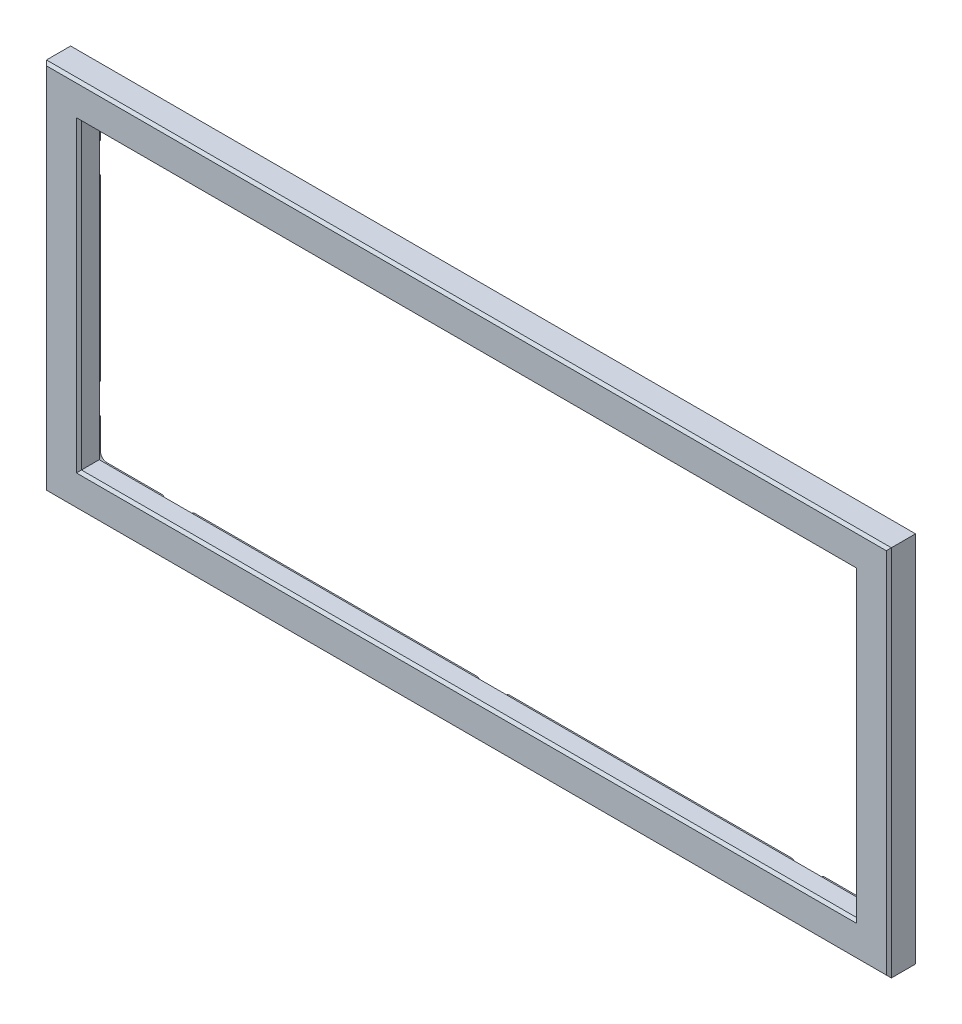
SolidWorks part; units mm, degrees
material "7075-T6 (SN)"
ref_plane "Front Plane" through (0, 0, 0) normal (0, 0, 1) x (1, 0, 0)
ref_plane "Top Plane" through (0, 0, 0) normal (0, 1, 0) x (1, 0, 0)
ref_plane "Right Plane" through (0, 0, 0) normal (1, 0, 0) x (0, 0, -1)
sketch "Sketch1" plane through (0, 0, 0) normal (0, 0, 1) x (1, 0, 0)
  line L43 (-4.2125, 142.325) -> (328.0625, 142.325)
  line L44 (-4.2125, 142.325) -> (-4.2125, -4.2125)
  line L45 (-4.2125, -4.2125) -> (328.0625, -4.2125)
  line L46 (328.0625, 142.325) -> (328.0625, -4.2125)
  line L104 (313.8, 130.5625) -> (292.3, 130.5625)
  line L105 (290.8, 132.0625) -> (290.8, 132.5625)
  line L106 (280.8, 132.5625) -> (280.8, 132.0625)
  line L107 (279.3, 130.5625) -> (168.425, 130.5625)
  line L108 (166.925, 132.0625) -> (166.925, 132.5625)
  line L109 (156.925, 132.5625) -> (156.925, 132.0625)
  line L110 (155.425, 130.5625) -> (44.55, 130.5625)
  line L111 (43.05, 132.0625) -> (43.05, 132.5625)
  line L112 (33.05, 132.5625) -> (33.05, 132.0625)
  line L113 (31.55, 130.5625) -> (10.05, 130.5625)
  line L114 (7.55, 128.0625) -> (7.55, 116.5625)
  line L115 (6.05, 115.0625) -> (5.55, 115.0625)
  line L116 (5.55, 105.0625) -> (6.05, 105.0625)
  line L117 (7.55, 103.5625) -> (7.55, 34.55)
  line L118 (6.05, 33.05) -> (5.55, 33.05)
  line L119 (5.55, 23.05) -> (6.05, 23.05)
  line L120 (7.55, 21.55) -> (7.55, 10.05)
  line L121 (10.05, 7.55) -> (31.55, 7.55)
  line L122 (33.05, 6.05) -> (33.05, 5.55)
  line L123 (43.05, 5.55) -> (43.05, 6.05)
  line L124 (44.55, 7.55) -> (155.425, 7.55)
  line L125 (156.925, 6.05) -> (156.925, 5.55)
  line L126 (166.925, 5.55) -> (166.925, 6.05)
  line L127 (168.425, 7.55) -> (279.3, 7.55)
  line L128 (280.8, 6.05) -> (280.8, 5.55)
  line L129 (290.8, 5.55) -> (290.8, 6.05)
  line L130 (292.3, 7.55) -> (313.8, 7.55)
  line L131 (316.3, 10.05) -> (316.3, 21.55)
  line L132 (317.8, 23.05) -> (318.3, 23.05)
  line L133 (318.3, 33.05) -> (317.8, 33.05)
  line L134 (316.3, 34.55) -> (316.3, 103.5625)
  line L135 (317.8, 105.0625) -> (318.3, 105.0625)
  line L136 (318.3, 115.0625) -> (317.8, 115.0625)
  line L137 (316.3, 116.5625) -> (316.3, 128.0625)
  line L138 (313.8, 130.5625) -> (292.3, 130.5625)
  line L139 (290.8, 132.0625) -> (290.8, 132.5625)
  line L140 (280.8, 132.5625) -> (280.8, 132.0625)
  line L141 (279.3, 130.5625) -> (168.425, 130.5625)
  line L142 (166.925, 132.0625) -> (166.925, 132.5625)
  line L143 (156.925, 132.5625) -> (156.925, 132.0625)
  line L144 (155.425, 130.5625) -> (44.55, 130.5625)
  line L145 (43.05, 132.0625) -> (43.05, 132.5625)
  line L146 (33.05, 132.5625) -> (33.05, 132.0625)
  line L147 (31.55, 130.5625) -> (10.05, 130.5625)
  line L148 (7.55, 128.0625) -> (7.55, 116.5625)
  line L149 (6.05, 115.0625) -> (5.55, 115.0625)
  line L150 (5.55, 105.0625) -> (6.05, 105.0625)
  line L151 (7.55, 103.5625) -> (7.55, 34.55)
  line L152 (6.05, 33.05) -> (5.55, 33.05)
  line L153 (5.55, 23.05) -> (6.05, 23.05)
  line L154 (7.55, 21.55) -> (7.55, 10.05)
  line L155 (10.05, 7.55) -> (31.55, 7.55)
  line L156 (33.05, 6.05) -> (33.05, 5.55)
  line L157 (43.05, 5.55) -> (43.05, 6.05)
  line L158 (44.55, 7.55) -> (155.425, 7.55)
  line L159 (156.925, 6.05) -> (156.925, 5.55)
  line L160 (166.925, 5.55) -> (166.925, 6.05)
  line L161 (168.425, 7.55) -> (279.3, 7.55)
  line L162 (280.8, 6.05) -> (280.8, 5.55)
  line L163 (290.8, 5.55) -> (290.8, 6.05)
  line L164 (292.3, 7.55) -> (313.8, 7.55)
  line L165 (316.3, 10.05) -> (316.3, 21.55)
  line L166 (317.8, 23.05) -> (318.3, 23.05)
  line L167 (318.3, 33.05) -> (317.8, 33.05)
  line L168 (316.3, 34.55) -> (316.3, 103.5625)
  line L169 (317.8, 105.0625) -> (318.3, 105.0625)
  line L170 (318.3, 115.0625) -> (317.8, 115.0625)
  line L171 (316.3, 116.5625) -> (316.3, 128.0625)
  arc A136 (290.8, 132.0625) -> (292.3, 130.5625) centre (292.3, 132.0625) ccw
  arc A137 (290.8, 132.5625) -> (280.8, 132.5625) centre (285.8, 132.5625) ccw
  arc A138 (279.3, 130.5625) -> (280.8, 132.0625) centre (279.3, 132.0625) ccw
  arc A139 (166.925, 132.0625) -> (168.425, 130.5625) centre (168.425, 132.0625) ccw
  arc A140 (166.925, 132.5625) -> (156.925, 132.5625) centre (161.925, 132.5625) ccw
  arc A141 (155.425, 130.5625) -> (156.925, 132.0625) centre (155.425, 132.0625) ccw
  arc A142 (43.05, 132.0625) -> (44.55, 130.5625) centre (44.55, 132.0625) ccw
  arc A143 (43.05, 132.5625) -> (33.05, 132.5625) centre (38.05, 132.5625) ccw
  arc A144 (31.55, 130.5625) -> (33.05, 132.0625) centre (31.55, 132.0625) ccw
  arc A145 (10.05, 130.5625) -> (7.55, 128.0625) centre (10.05, 128.0625) ccw
  arc A146 (6.05, 115.0625) -> (7.55, 116.5625) centre (6.05, 116.5625) ccw
  arc A147 (5.55, 115.0625) -> (5.55, 105.0625) centre (5.55, 110.0625) ccw
  arc A148 (7.55, 103.5625) -> (6.05, 105.0625) centre (6.05, 103.5625) ccw
  arc A149 (6.05, 33.05) -> (7.55, 34.55) centre (6.05, 34.55) ccw
  arc A150 (5.55, 33.05) -> (5.55, 23.05) centre (5.55, 28.05) ccw
  arc A151 (7.55, 21.55) -> (6.05, 23.05) centre (6.05, 21.55) ccw
  arc A152 (7.55, 10.05) -> (10.05, 7.55) centre (10.05, 10.05) ccw
  arc A153 (33.05, 6.05) -> (31.55, 7.55) centre (31.55, 6.05) ccw
  arc A154 (33.05, 5.55) -> (43.05, 5.55) centre (38.05, 5.55) ccw
  arc A155 (44.55, 7.55) -> (43.05, 6.05) centre (44.55, 6.05) ccw
  arc A156 (156.925, 6.05) -> (155.425, 7.55) centre (155.425, 6.05) ccw
  arc A157 (156.925, 5.55) -> (166.925, 5.55) centre (161.925, 5.55) ccw
  arc A158 (168.425, 7.55) -> (166.925, 6.05) centre (168.425, 6.05) ccw
  arc A159 (280.8, 6.05) -> (279.3, 7.55) centre (279.3, 6.05) ccw
  arc A160 (280.8, 5.55) -> (290.8, 5.55) centre (285.8, 5.55) ccw
  arc A161 (292.3, 7.55) -> (290.8, 6.05) centre (292.3, 6.05) ccw
  arc A162 (313.8, 7.55) -> (316.3, 10.05) centre (313.8, 10.05) ccw
  arc A163 (317.8, 23.05) -> (316.3, 21.55) centre (317.8, 21.55) ccw
  arc A164 (318.3, 23.05) -> (318.3, 33.05) centre (318.3, 28.05) ccw
  arc A165 (316.3, 34.55) -> (317.8, 33.05) centre (317.8, 34.55) ccw
  arc A166 (317.8, 105.0625) -> (316.3, 103.5625) centre (317.8, 103.5625) ccw
  arc A167 (318.3, 105.0625) -> (318.3, 115.0625) centre (318.3, 110.0625) ccw
  arc A168 (316.3, 116.5625) -> (317.8, 115.0625) centre (317.8, 116.5625) ccw
  arc A169 (316.3, 128.0625) -> (313.8, 130.5625) centre (313.8, 128.0625) ccw
  arc A170 (290.8, 132.0625) -> (292.3, 130.5625) centre (292.3, 132.0625) ccw
  arc A171 (290.8, 132.5625) -> (280.8, 132.5625) centre (285.8, 132.5625) ccw
  arc A172 (279.3, 130.5625) -> (280.8, 132.0625) centre (279.3, 132.0625) ccw
  arc A173 (166.925, 132.0625) -> (168.425, 130.5625) centre (168.425, 132.0625) ccw
  arc A174 (166.925, 132.5625) -> (156.925, 132.5625) centre (161.925, 132.5625) ccw
  arc A175 (155.425, 130.5625) -> (156.925, 132.0625) centre (155.425, 132.0625) ccw
  arc A176 (43.05, 132.0625) -> (44.55, 130.5625) centre (44.55, 132.0625) ccw
  arc A177 (43.05, 132.5625) -> (33.05, 132.5625) centre (38.05, 132.5625) ccw
  arc A178 (31.55, 130.5625) -> (33.05, 132.0625) centre (31.55, 132.0625) ccw
  arc A179 (10.05, 130.5625) -> (7.55, 128.0625) centre (10.05, 128.0625) ccw
  arc A180 (6.05, 115.0625) -> (7.55, 116.5625) centre (6.05, 116.5625) ccw
  arc A181 (5.55, 115.0625) -> (5.55, 105.0625) centre (5.55, 110.0625) ccw
  arc A182 (7.55, 103.5625) -> (6.05, 105.0625) centre (6.05, 103.5625) ccw
  arc A183 (6.05, 33.05) -> (7.55, 34.55) centre (6.05, 34.55) ccw
  arc A184 (5.55, 33.05) -> (5.55, 23.05) centre (5.55, 28.05) ccw
  arc A185 (7.55, 21.55) -> (6.05, 23.05) centre (6.05, 21.55) ccw
  arc A186 (7.55, 10.05) -> (10.05, 7.55) centre (10.05, 10.05) ccw
  arc A187 (33.05, 6.05) -> (31.55, 7.55) centre (31.55, 6.05) ccw
  arc A188 (33.05, 5.55) -> (43.05, 5.55) centre (38.05, 5.55) ccw
  arc A189 (44.55, 7.55) -> (43.05, 6.05) centre (44.55, 6.05) ccw
  arc A190 (156.925, 6.05) -> (155.425, 7.55) centre (155.425, 6.05) ccw
  arc A191 (156.925, 5.55) -> (166.925, 5.55) centre (161.925, 5.55) ccw
  arc A192 (168.425, 7.55) -> (166.925, 6.05) centre (168.425, 6.05) ccw
  arc A193 (280.8, 6.05) -> (279.3, 7.55) centre (279.3, 6.05) ccw
  arc A194 (280.8, 5.55) -> (290.8, 5.55) centre (285.8, 5.55) ccw
  arc A195 (292.3, 7.55) -> (290.8, 6.05) centre (292.3, 6.05) ccw
  arc A196 (313.8, 7.55) -> (316.3, 10.05) centre (313.8, 10.05) ccw
  arc A197 (317.8, 23.05) -> (316.3, 21.55) centre (317.8, 21.55) ccw
  arc A198 (318.3, 23.05) -> (318.3, 33.05) centre (318.3, 28.05) ccw
  arc A199 (316.3, 34.55) -> (317.8, 33.05) centre (317.8, 34.55) ccw
  arc A200 (317.8, 105.0625) -> (316.3, 103.5625) centre (317.8, 103.5625) ccw
  arc A201 (318.3, 105.0625) -> (318.3, 115.0625) centre (318.3, 110.0625) ccw
  arc A202 (316.3, 116.5625) -> (317.8, 115.0625) centre (317.8, 116.5625) ccw
  arc A203 (316.3, 128.0625) -> (313.8, 130.5625) centre (313.8, 128.0625) ccw
  dimension "D2" = 4.7625
  dimension "D3" = 4.7625
  dimension "D4" = 4.7625
  dimension "D5" = 4.7625
  dimension "D1" = 0.5
extrude "Boss-Extrude1" add sketch "Sketch1" against normal mid plane 2.5
sketch "Sketch2" plane through (0, 0, 1.25) normal (0, 0, 1) x (1, 0, 0)
  line L28 (7.55, 128.0625) -> (7.55, 116.5625) construction
  line L30 (161.925, 142.325) -> (161.925, -4.2125) construction
  line L31 (-4.2125, 69.0562) -> (328.0625, 69.0562) construction
  line L32 (328.0625, -4.2125) -> (328.0625, 142.325) construction
  line L36 (328.0625, 142.325) -> (-4.2125, 142.325)
  line L38 (-4.2125, 142.325) -> (-4.2125, -4.2125)
  line L39 (9.55, 128.5625) -> (314.3, 128.5625)
  line L40 (-4.2125, -4.2125) -> (328.0625, -4.2125)
  line L41 (9.55, 128.5625) -> (9.55, 9.55)
  line L42 (328.0625, -4.2125) -> (328.0625, 142.325)
  line L43 (9.55, 9.55) -> (314.3, 9.55)
  line L44 (328.0625, 142.325) -> (-4.2125, 142.325)
  line L46 (-4.2125, 142.325) -> (-4.2125, -4.2125)
  line L48 (-4.2125, -4.2125) -> (328.0625, -4.2125)
  line L50 (328.0625, -4.2125) -> (328.0625, 142.325)
  line L52 (314.3, 128.5625) -> (314.3, 9.55)
  dimension "D2" = 11.7625
  dimension "D3" = 13.7625
  dimension "D4" = 13.7625
  dimension "D5" = 13.7625
  dimension "D6" = 13.7625
extrude "Boss-Extrude2" add sketch "Sketch2" along normal blind 8 contours L50 L44 L46 L48 region at (324.431, 69.0562, 1.25)
chamfer "Chamfer1" distance 1 angle 45 8 edges at (328.0625, 69.0562, 9.25) (161.925, -4.2125, 9.25) (-4.2125, 69.0562, 9.25) (161.925, 142.325, 9.25) (9.55, 69.0562, 9.25) (161.925, 9.55, 9.25) (314.3, 69.0562, 9.25) (161.925, 128.5625, 9.25)
hole_wizard "M2.5 Tapped Hole1" positions "Sketch3" profile "Sketch4" tap size "M2.5" standard "DIN"
sketch "Sketch3" plane through (0, 0, 1.25) normal (0, 0, -1) x (-1, 0, 0)
  arc A1 (-290.8, 5.55) -> (-280.8, 5.55) centre (-285.8, 5.55) ccw construction
  point P37 (-285.8, 132.5625)
  point P40 (-318.3, 110.0625)
  point P43 (-318.3, 28.05)
  point P46 (-285.8, 5.55)
  point P49 (-161.925, 5.55)
  point P52 (-38.05, 5.55)
  point P55 (-5.55, 28.05)
  point P58 (-38.05, 132.5625)
  point P61 (-5.55, 110.0625)
  point P65 (-161.925, 132.5625)
sketch "Sketch4" plane through (285.8, 132.5625, 1.25) normal (1, 0, 0) x (0, 1, 0)
  line L0 (0, 0) -> (0, 6.9659)
  line L1 (0, 6.9659) -> (1.025, 6.35)
  line L2 (1.025, 6.35) -> (1.025, 0.475)
  line L3 (1.025, 0.475) -> (1.5, 0)
  line L5 (1.5, 0) -> (0, 0)
  line L6 (-1.025, 0.475) -> (-1.5, 0) construction
  line L10 (0, 6.9659) -> (-1.025, 6.35) construction
  line L11 (0, -6.35) -> (0, 107.95) construction
  dimension "Tap Drill Dia." = 2.05
  dimension "Tap Drill Depth" = 6.35
  dimension "Near C'Sink Dia." = 3
  dimension "Near C'Sink Angle" = 90
  dimension "Drill Angle" = 118
cosmetic thread "Hole Thread44" parameters "D1"=5, "D2"=2.5
cosmetic thread "Hole Thread45" parameters "D1"=5, "D2"=2.5
cosmetic thread "Hole Thread46" parameters "D1"=5, "D2"=2.5
cosmetic thread "Hole Thread47" parameters "D1"=5, "D2"=2.5
cosmetic thread "Hole Thread48" parameters "D1"=5, "D2"=2.5
cosmetic thread "Hole Thread49" parameters "D1"=5, "D2"=2.5
cosmetic thread "Hole Thread50" parameters "D1"=5, "D2"=2.5
cosmetic thread "Hole Thread51" parameters "D1"=5, "D2"=2.5
cosmetic thread "Hole Thread52" parameters "D1"=5, "D2"=2.5
cosmetic thread "Hole Thread53" parameters "D1"=5, "D2"=2.5
hole_wizard "M3 Tapped Hole1" positions "Sketch5" profile "Sketch6" tap size "M3" standard "DIN"
sketch "Sketch5" plane through (0, 0, -1.25) normal (0, 0, -1) x (-1, 0, 0)
  point P0 (-268.0625, 138.325)
  point P3 (-324.0625, 138.325)
  point P6 (-324.0625, 88.325)
  point P9 (-324.0625, 49.7874)
  point P12 (-324.0625, -0.2126)
  point P15 (-268.0625, -0.2126)
  point P18 (-201.925, 138.325)
  point P21 (-201.925, -0.2126)
  point P24 (-121.925, -0.2126)
  point P27 (-55.7875, -0.2126)
  point P30 (0.2125, -0.2126)
  point P33 (0.2125, 49.7874)
  point P36 (0.2125, 88.325)
  point P39 (0.2125, 138.325)
  point P42 (-55.7875, 138.325)
  point P45 (-121.925, 138.325)
sketch "Sketch6" plane through (268.0625, 138.325, -1.25) normal (1, 0, 0) x (0, 1, 0)
  line L0 (0, 0) -> (0, 6.7511)
  line L1 (0, 6.7511) -> (1.25, 6)
  line L2 (1.25, 6) -> (1.25, 0.5)
  line L3 (1.25, 0.5) -> (1.75, 0)
  line L5 (1.75, 0) -> (0, 0)
  line L6 (-1.25, 0.5) -> (-1.75, 0) construction
  line L10 (0, 6.7511) -> (-1.25, 6) construction
  line L11 (0, -6.35) -> (0, 107.95) construction
  dimension "Tap Drill Dia." = 2.5
  dimension "Tap Drill Depth" = 6
  dimension "Near C'Sink Dia." = 3.5
  dimension "Near C'Sink Angle" = 90
  dimension "Drill Angle" = 118
cosmetic thread "Hole Thread28" parameters "D1"=6, "D2"=3
cosmetic thread "Hole Thread29" parameters "D1"=6, "D2"=3
cosmetic thread "Hole Thread30" parameters "D1"=6, "D2"=3
cosmetic thread "Hole Thread31" parameters "D1"=6, "D2"=3
cosmetic thread "Hole Thread32" parameters "D1"=6, "D2"=3
cosmetic thread "Hole Thread33" parameters "D1"=6, "D2"=3
cosmetic thread "Hole Thread34" parameters "D1"=6, "D2"=3
cosmetic thread "Hole Thread35" parameters "D1"=6, "D2"=3
cosmetic thread "Hole Thread36" parameters "D1"=6, "D2"=3
cosmetic thread "Hole Thread37" parameters "D1"=6, "D2"=3
cosmetic thread "Hole Thread38" parameters "D1"=6, "D2"=3
cosmetic thread "Hole Thread39" parameters "D1"=6, "D2"=3
cosmetic thread "Hole Thread40" parameters "D1"=6, "D2"=3
cosmetic thread "Hole Thread41" parameters "D1"=6, "D2"=3
cosmetic thread "Hole Thread42" parameters "D1"=6, "D2"=3
cosmetic thread "Hole Thread43" parameters "D1"=6, "D2"=3
equation "\"D2@Sketch1\"=\"D3@Sketch1\""
equation "\"D4@Sketch1\"=\"D3@Sketch1\""
equation "\"D5@Sketch1\"=\"D3@Sketch1\""
equation "\"D3@Sketch2\"=\"D2@Sketch2\"+2"
equation "\"D4@Sketch2\"=\"D3@Sketch2\""
equation "\"D5@Sketch2\"=\"D3@Sketch2\""
equation "\"D6@Sketch2\"=\"D3@Sketch2\""
